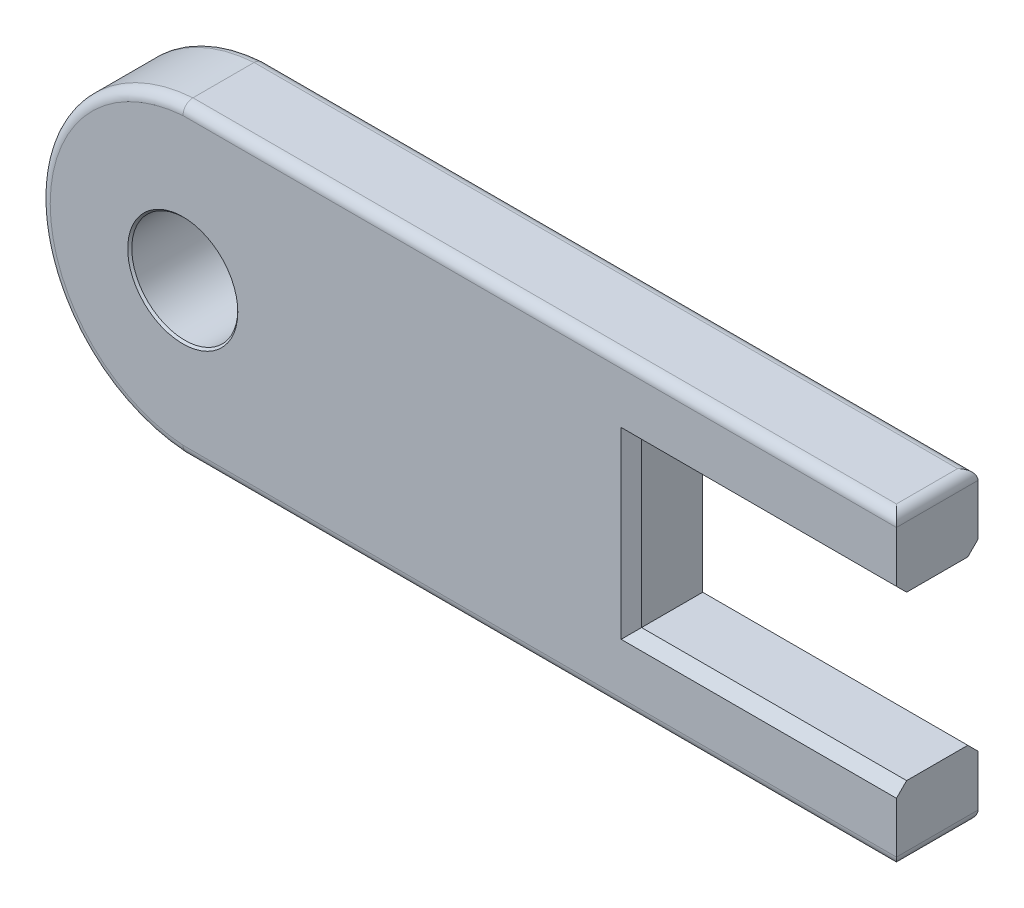
SolidWorks part; units mm, degrees
ref_plane "Front Plane" through (0, 0, 0) normal (0, 0, 1) x (1, 0, 0)
ref_plane "Top Plane" through (0, 0, 0) normal (0, 1, 0) x (1, 0, 0)
ref_plane "Right Plane" through (0, 0, 0) normal (1, 0, 0) x (0, 0, -1)
sketch "Sketch1" plane through (0, 0, 0) normal (0, 0, 1) x (1, 0, 0)
  line L0 (-208.7746, 0) -> (131.2254, 0) construction
  line L1 (-276.9158, 75) -> (73.0842, 75)
  line L3 (-276.9158, -75) -> (73.0842, -75)
  line L4 (73.0842, 75) -> (73.0842, 40)
  line L5 (73.0842, 40) -> (-56.9158, 40)
  line L10 (-56.9158, 40) -> (-56.9158, -40)
  line L11 (-56.9158, -40) -> (73.0842, -40)
  line L12 (73.0842, -40) -> (73.0842, -75)
  circle A1 centre (-276.9158, 0) radius 26
  arc A2 (-276.9158, 75) -> (-276.9158, -75) centre (-271.7372, 0) ccw
  dimension "D6" = 70
  dimension "D2" = 420
  dimension "D7" = 52
  dimension "D8" = 350
  dimension "D1" = 150
  dimension "D3" = 130
  dimension "D4" = 80
  dimension "D5" = 80
extrude "Boss-Extrude1" add sketch "Sketch1" along normal mid plane 40 contours L1 L4 L5 L10 L11 L12 L3 A2
sketch "Sketch2" plane through (0, 0, 20) normal (0, 0, 1) x (1, 0, 0)
  line L0 (0, 0) -> (-346.9158, 0) construction
  circle A0 centre (-276.9158, 0) radius 26
  arc A4 (-276.9158, 75) -> (-276.9158, -75) centre (-271.7372, 0) ccw construction
  dimension "D1" = 52
  dimension "D2" = 70
extrude "Cut-Extrude1" cut sketch "Sketch2" against normal blind 40
fillet "Fillet1" radius 5 8 edges at (-101.9158, -75, -20) (-101.9158, 75, -20) (-346.9158, 0, -20) (-101.9158, -75, 20) (-346.9158, 0, 20) (-101.9158, 75, 20) (73.0842, -75, 0) (73.0842, 75, 0)
chamfer "Chamfer1" distance 1 angle 45 2 edges at (-250.9158, 0, 20) (-250.9158, 0, -20)
chamfer "Chamfer2" distance 5 angle 45 6 edges at (8.0842, 40, -20) (-56.9158, 0, -20) (8.0842, -40, -20) (8.0842, 40, 20) (-56.9158, 0, 20) (8.0842, -40, 20)
